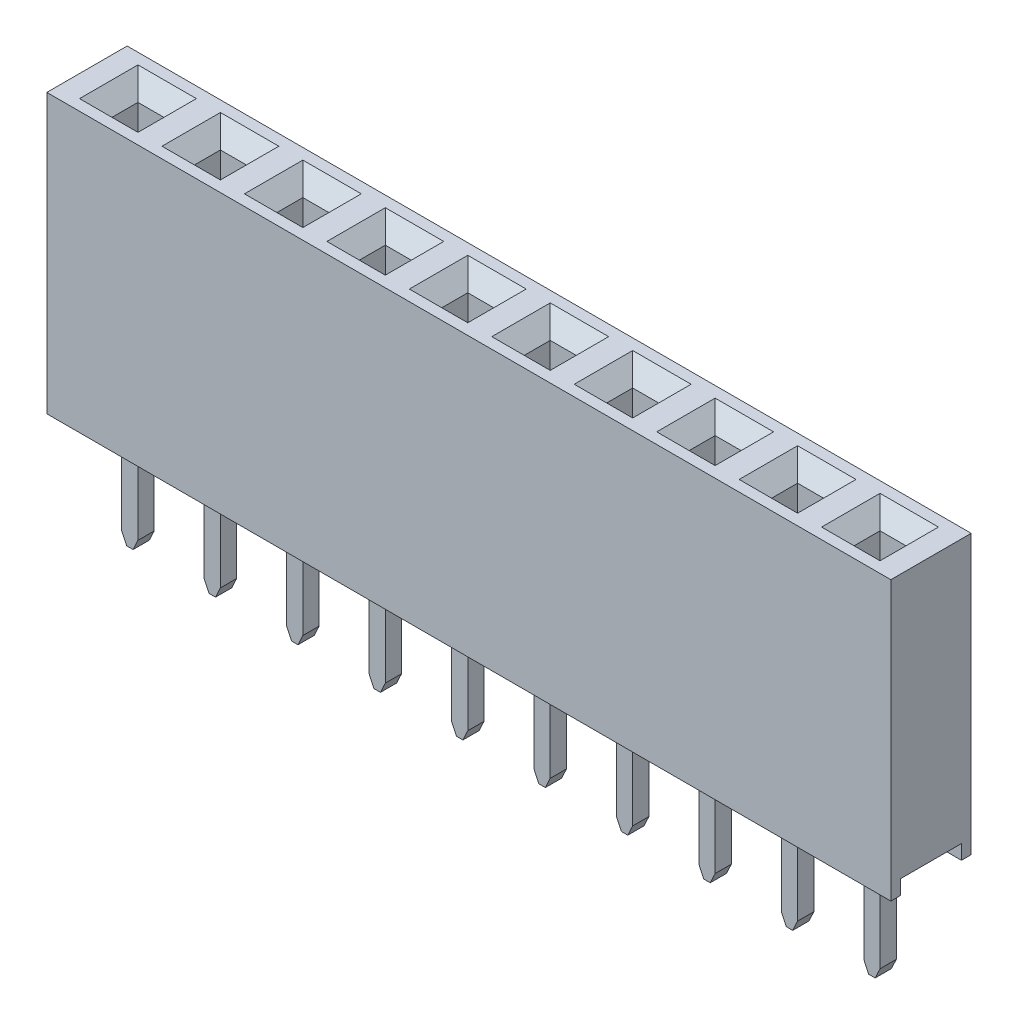
SolidWorks part; units mm, degrees
note: The reader was unsure of these and kept them because the rebuilt part matched: shared geometry of "Sketch9<3>".
ref_plane "Front" through (0, 0, 0) normal (0, 0, 1) x (1, 0, 0)
ref_plane "Top" through (0, 0, 0) normal (0, 1, 0) x (1, 0, 0)
ref_plane "Right" through (0, 0, 0) normal (1, 0, 0) x (0, 0, -1)
sketch "Sketch1" plane through (0, 0, 0) normal (0, 0, 1) x (1, 0, 0)
  line L1 (13, -4.2875) -> (-13, -4.2875)
  line L2 (13, -4.2875) -> (13, 4.2875)
  line L3 (13, 4.2875) -> (-13, 4.2875)
  line L4 (-13, -4.2875) -> (-13, 4.2875)
  line L5 (13, -4.2875) -> (-13, 4.2875) construction
  line L6 (13, 4.2875) -> (-13, -4.2875) construction
  point P0 (0, 0)
  dimension "D1" = 26
  dimension "D2" = 8.575
extrude "Boss-Extrude1" add sketch "Sketch1" along normal mid plane 2.475
sketch "Sketch2" plane through (0, 0, 0) normal (1, 0, 0) x (0, 0, -1)
  line L0 (-0.9375, -4.2875) -> (0.9375, -4.2875)
  line L1 (-1.2375, -4.2875) -> (1.2375, -4.2875) construction
  line L2 (0.9375, -4.2875) -> (0.9375, -3.8396)
  line L3 (0.9375, -3.8396) -> (-0.9375, -3.8396)
  line L4 (-0.9375, -3.8396) -> (-0.9375, -4.2875)
  line L5 (1.2375, -4.2875) -> (1.2375, 4.2875) construction
  line L6 (-1.2375, -4.2875) -> (-1.2375, 4.2875) construction
  dimension "D1" = 0.3
  dimension "D2" = 0.3
extrude "Cut-Extrude1" cut sketch "Sketch2" against normal mid plane 100
sketch "Sketch4" plane through (0, 4.2875, 0) normal (0, 1, 0) x (1, 0, 0)
  line L0 (-13, 0) -> (13, 0) construction
  line L1 (-13, -1.2375) -> (-13, 1.2375) construction
  line L2 (13, -1.2375) -> (13, 1.2375) construction
  line L4 (-12.305, 0.875) -> (-10.555, 0.875)
  line L5 (-12.305, 0.875) -> (-12.305, -0.875)
  line L6 (-12.305, -0.875) -> (-10.555, -0.875)
  line L7 (-10.555, 0.875) -> (-10.555, -0.875)
  line L8 (-12.305, 0.875) -> (-10.555, -0.875) construction
  line L9 (-12.305, -0.875) -> (-10.555, 0.875) construction
  line L10 (-11.83, 0.4) -> (-11.03, 0.4)
  line L11 (-11.83, 0.4) -> (-11.83, -0.4)
  line L12 (-11.83, -0.4) -> (-11.03, -0.4)
  line L13 (-11.03, 0.4) -> (-11.03, -0.4)
  line L14 (-11.83, 0.4) -> (-11.03, -0.4) construction
  line L15 (-11.83, -0.4) -> (-11.03, 0.4) construction
  point P6 (-11.43, 0)
  point P11 (-11.43, 0)
  point P16 (-6.0293, 0)
  point P17 (-1.9466, 0)
  point P18 (0, 0)
  dimension "D1" = 1.75
  dimension "D2" = 0.8
  dimension "D3" = 1.57
extrude "Cut-Extrude2" cut sketch "Sketch4" against normal blind 1.5 contours L13 L10 L11 L12
chamfer "Chamfer1" distance 0.5 angle 45 4 edges at (-11.43, 4.2875, -0.4) (-11.83, 4.2875, 0) (-11.43, 4.2875, 0.4) (-11.03, 4.2875, 0)
sketch "Sketch5" plane through (0, 0, 0) normal (0, 1, 0) x (1, 0, 0)
  line L1 (-12.33, 0.9) -> (-10.53, 0.9)
  line L2 (-12.33, 0.9) -> (-12.33, -0.9)
  line L3 (-12.33, -0.9) -> (-10.53, -0.9)
  line L4 (-10.53, 0.9) -> (-10.53, -0.9)
extrude "Cut-Extrude3" cut sketch "Sketch5" against normal blind 3 and the other way blind 3
sketch "Sketch9" plane through (0, 0, 0) normal (0, 0, 1) x (1, 0, 0)
  line L0 (-11.43, 1.5354) -> (-11.43, -7.5678) construction
  line L1 (-11.68, -3) -> (-11.7107, -3)
  line L2 (-11.7005, 1.5354) -> (-11.43, 1.5354) construction
  line L3 (-11.7103, 1.3926) -> (-11.7005, 1.5354) construction
  line L4 (-11.33, -7.5678) -> (-11.18, -7.2462)
  line L5 (-11.18, -7.2462) -> (-11.18, -3)
  line L6 (-11.18, -3) -> (-11.1493, -3)
  line L7 (-12.2828, -2.64) -> (-11.7107, -3)
  line L8 (-12.2828, -1.2883) -> (-12.2828, -2.64)
  line L9 (-12.2828, -1.2883) -> (-12.0322, -1.2076)
  line L10 (-12.0322, -1.2076) -> (-11.8433, 1.5452)
  line L11 (-11.7103, 1.3926) -> (-11.9375, -1.9184)
  line L12 (-11.53, -7.5678) -> (-11.33, -7.5678)
  line L13 (-10.5772, -2.64) -> (-11.1493, -3)
  line L14 (-11.1497, 1.3926) -> (-10.9225, -1.9184)
  line L15 (-11.53, -7.5678) -> (-11.68, -7.2462)
  line L16 (-11.68, -7.2462) -> (-11.68, -3)
  line L17 (-13, -4.2875) -> (13, -4.2875) construction
  line L18 (-10.5772, -1.2883) -> (-10.8278, -1.2076)
  line L19 (-10.8278, -1.2076) -> (-11.0167, 1.5452)
  line L20 (-10.5772, -1.2883) -> (-10.5772, -2.64)
  line L21 (-11.43, 3.7875) -> (-11.43, 1.5354) construction
  line L22 (-11.83, 3.7875) -> (-11.03, 3.7875) construction
  line L23 (-10.53, -3) -> (-12.33, -3) construction
  line L24 (-11.18, -3) -> (-11.68, -3)
  arc A0 (-11.0167, 1.5452) -> (-11.1497, 1.3926) centre (-11.1595, 1.5354) ccw
  arc A1 (-10.9225, -1.9184) -> (-11.43, -2.341) centre (-11.329, -1.9463) cw
  arc A2 (-11.9375, -1.9184) -> (-11.43, -2.341) centre (-11.531, -1.9463) ccw
  arc A3 (-11.8433, 1.5452) -> (-11.7103, 1.3926) centre (-11.7005, 1.5354) cw
  point P0 (-11.43, -4.2875)
  point P16 (-11.43, -3.8933)
  point P24 (-11.68, -4.2875)
  point P37 (-11.1493, -3)
  dimension "D7" = 0.1431
  dimension "D8" = 0.36
  dimension "D12" = 0.4074
  dimension "D15" = 3.4817
  dimension "D1" = 0.3217
  dimension "D2" = 115
  dimension "D3" = 4.2462
  dimension "D4" = 0.1
  dimension "D5" = 0.25
  dimension "D6" = 0.0307
  dimension "D9" = 0.572
  dimension "D10" = 1.3517
  dimension "D11" = 0.6937
  dimension "D13" = 0.101
  dimension "D14" = 0.2705
  dimension "D16" = 0.0808
extrude "Boss-Extrude4" add sketch "Sketch9" along normal mid plane 1.7
extrude "Boss-Extrude5" add sketch "Sketch9<3>" along normal mid plane 0.5
sketch "Sketch9<3>" plane through (0, 0, 0) normal (0, 0, 1) x (1, 0, 0) same geometry as "Sketch9"
pattern_linear "LPattern1" count 10 spacing 2.54 along (1, 0, 0) of "Chamfer1", "Cut-Extrude3", "Boss-Extrude4", "Boss-Extrude5", "Cut-Extrude2"
